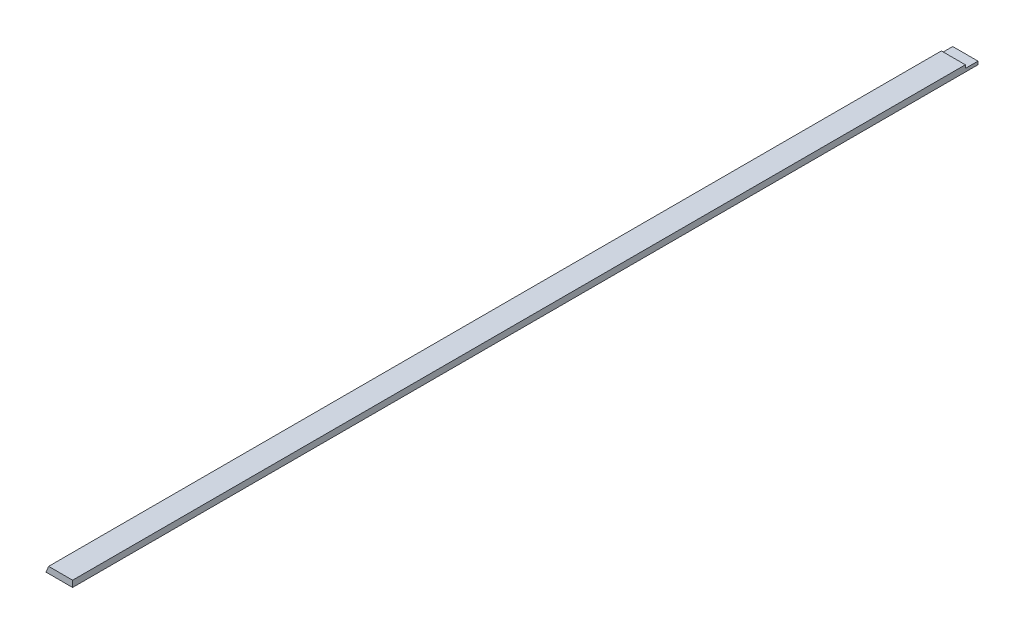
SolidWorks part; units mm, degrees
ref_plane "Front Plane" through (0, 0, 0) normal (0, 0, 1) x (1, 0, 0)
ref_plane "Top Plane" through (0, 0, 0) normal (0, 1, 0) x (1, 0, 0)
ref_plane "Right Plane" through (0, 0, 0) normal (1, 0, 0) x (0, 0, -1)
sketch "Sketch1" plane through (0, 0, 0) normal (0, 0, 1) x (1, 0, 0)
  line L0 (0, 0) -> (26.67, 0)
  line L1 (26.67, 0) -> (26.67, 6.35)
  line L2 (26.67, 6.35) -> (2.6303, 6.35)
  line L3 (2.6303, 6.35) -> (0, 0)
  dimension "D1" = 67.5
  dimension "D2" = 26.67
  dimension "D3" = 6.35
extrude "Boss-Extrude1" add sketch "Sketch1" along normal blind 908.05
sketch "Sketch2" plane through (0, 6.35, 0) normal (0, 1, 0) x (1, 0, 0)
  line L5 (26.67, -908.05) -> (26.67, 0) construction
  line L6 (0, 0) -> (26.67, 0)
  line L7 (0, 0) -> (0, -12.7)
  line L8 (0, -12.7) -> (26.67, -12.7)
  line L9 (26.67, 0) -> (26.67, -12.7)
  dimension "D1" = 12.7
extrude "Cut-Extrude1" cut sketch "Sketch2" against normal blind 3.175
